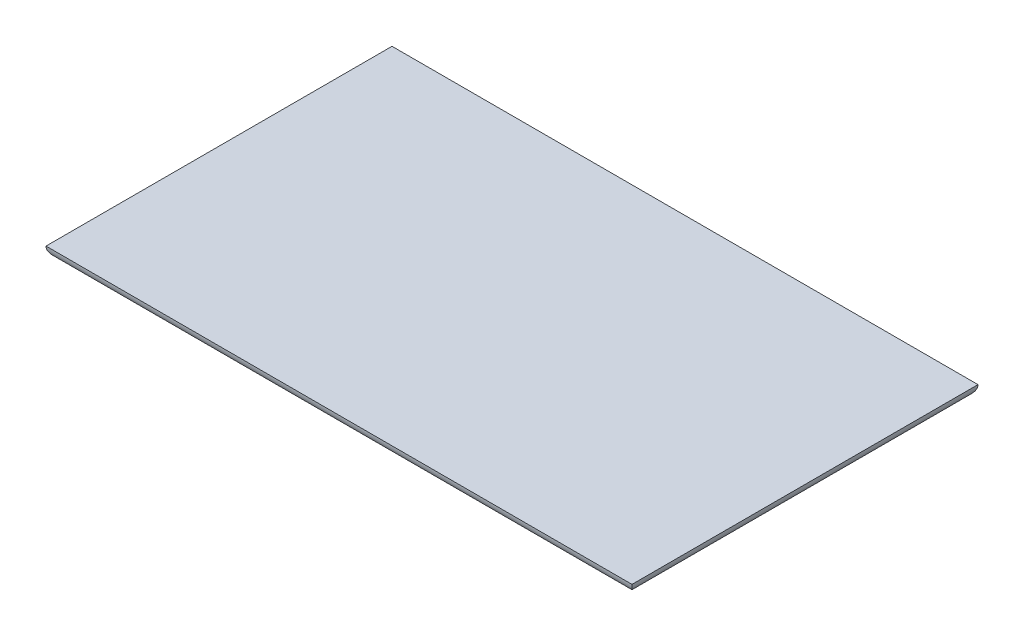
SolidWorks part; units mm, degrees
ref_plane "Front Plane" through (0, 0, 0) normal (0, 0, 1) x (1, 0, 0)
ref_plane "Top Plane" through (0, 0, 0) normal (0, 1, 0) x (1, 0, 0)
ref_plane "Right Plane" through (0, 0, 0) normal (1, 0, 0) x (0, 0, -1)
sketch "Sketch1" plane through (0, 0, 0) normal (0, 1, 0) x (1, 0, 0)
  line L0 (-47.9372, 26.7207) -> (-49.4372, 28.2207) construction
  line L1 (-47.9372, 26.7207) -> (54.0628, 26.7207)
  line L2 (-47.9372, 26.7207) -> (-47.9372, -32.2793)
  line L3 (-47.9372, -32.2793) -> (54.0628, -32.2793)
  line L4 (54.0628, 26.7207) -> (54.0628, -32.2793)
  line L5 (54.0628, -32.2793) -> (55.5628, -33.7793) construction
  line L7 (55.5628, -33.7793) -> (-49.4372, -33.7793)
  line L8 (55.5628, -33.7793) -> (55.5628, 28.2207)
  line L9 (55.5628, 28.2207) -> (-49.4372, 28.2207)
  line L10 (-49.4372, -33.7793) -> (-49.4372, 28.2207)
  dimension "D1" = 102
  dimension "D2" = 59
  dimension "D3" = 2.1213
  dimension "D4" = 2.1213
extrude "Boss-Extrude1" add sketch "Sketch1" along normal blind 2
extrude "Boss-Extrude2" add sketch "Sketch1<2>" along normal blind 2 contours L2 L3 L4 L1
sketch "Sketch1<2>" plane through (0, 0, 0) normal (0, 1, 0) x (1, 0, 0) same geometry as "Sketch1"
fillet "Fillet1" radius 2 4 edges at (3.0628, 0, 33.7793) (55.5628, 0, 2.7793) (3.0628, 0, -28.2207) (-49.4372, 0, 2.7793)
